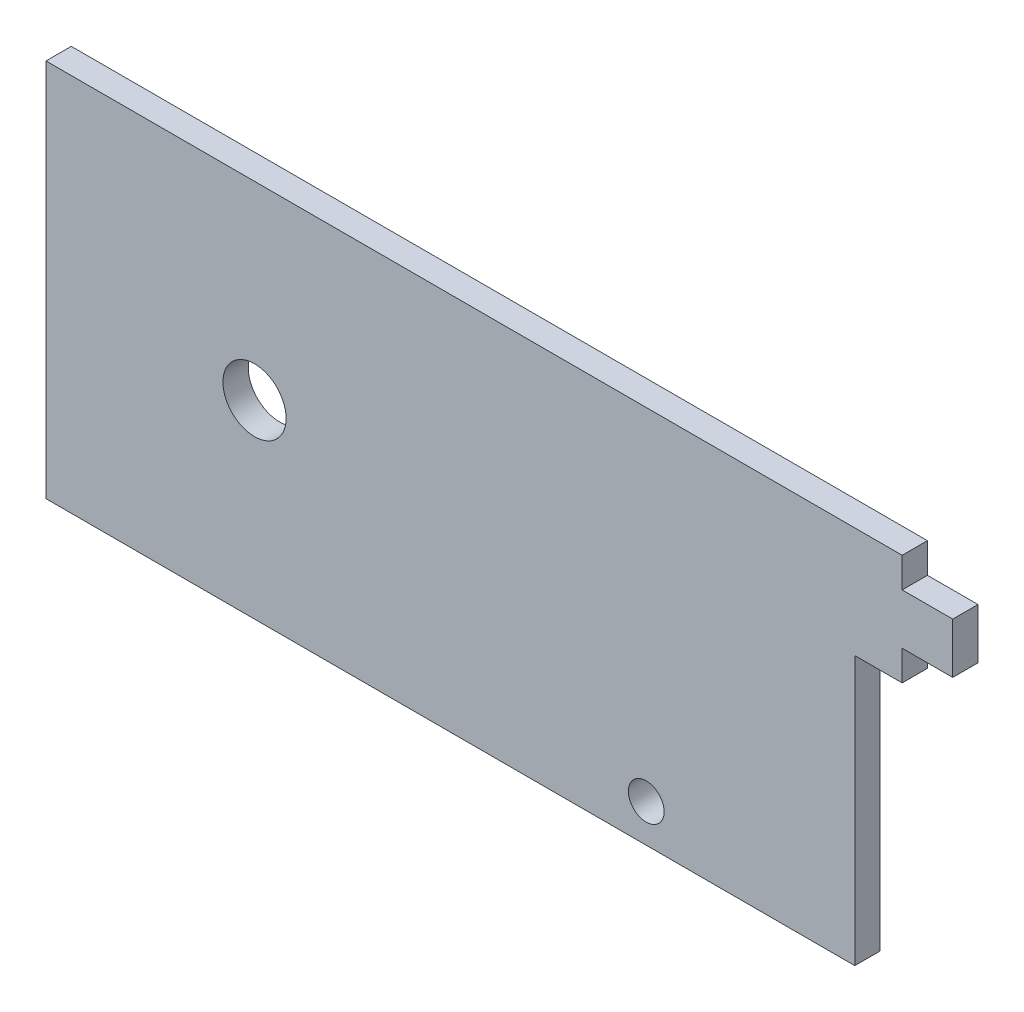
SolidWorks part; units mm, degrees
ref_plane "Front Plane" through (0, 0, 0) normal (0, 0, 1) x (1, 0, 0)
ref_plane "Top Plane" through (0, 0, 0) normal (0, 1, 0) x (1, 0, 0)
ref_plane "Right Plane" through (0, 0, 0) normal (1, 0, 0) x (0, 0, -1)
sketch "Sketch1" plane through (0, 0, 0) normal (0, 0, 1) x (1, 0, 0)
  line L0 (47, 30) -> (54.5, 30)
  line L1 (-81, -30) -> (47, -30)
  line L2 (-81, -30) -> (-81, 30)
  line L3 (-81, 30) -> (47, 30)
  line L4 (47, -30) -> (47, 30) construction
  line L6 (54.5, 12.5) -> (47, 12.5)
  line L11 (54.5, 30) -> (54.5, 12.5) construction
  line L12 (54.5, 30) -> (54.5, 25.25)
  line L13 (47, 12.5) -> (47, -30)
  line L14 (54.5, 25.25) -> (62.5, 25.25)
  line L15 (62.5, 25.25) -> (62.5, 17.25)
  line L16 (62.5, 17.25) -> (54.5, 17.25)
  line L17 (54.5, 17.25) -> (54.5, 12.5)
  circle A4 centre (-48, 0) radius 5
  circle A5 centre (14, -24) radius 2.83
  point P12 (-81, 0)
  dimension "D3" = 17.5
  dimension "D4" = 7.5
  dimension "D5" = 10
  dimension "D1" = 128
  dimension "D6" = 33
  dimension "D9" = 5.66
  dimension "D10" = 95
  dimension "D11" = 6
  dimension "D2" = 60
  dimension "D7" = 8
  dimension "D8" = 8
extrude "Boss-Extrude1" add sketch "Sketch1" along normal blind 4
